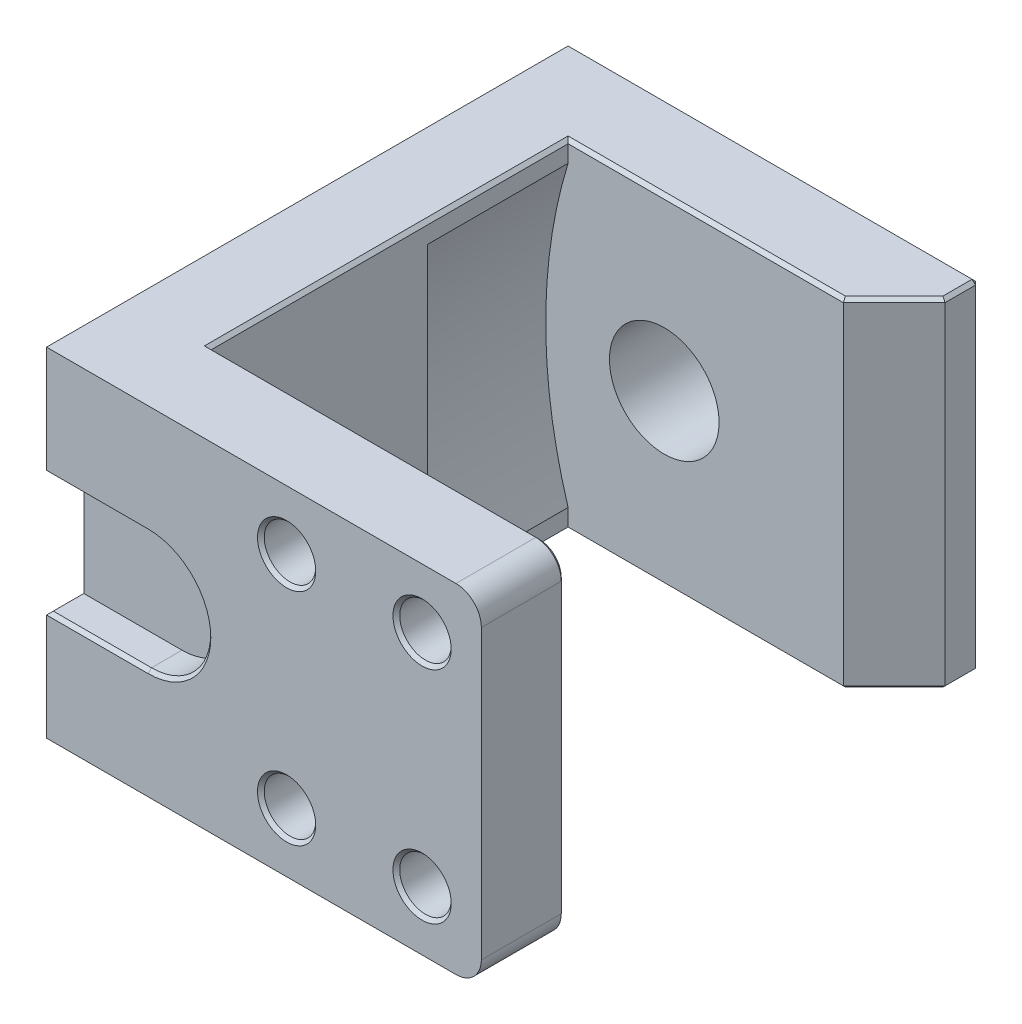
SolidWorks part; units mm, degrees
other "标注1"
sketch "草图9" plane through (-10.48, 10, -1.55) normal (-0.4516, 0.1897, -0.8718) x (-0.888, 0, 0.4599)
material "7075-T6 (SN)"
ref_plane "前视基准面" through (0, 0, 0) normal (0, 0, 1) x (1, 0, 0)
ref_plane "上视基准面" through (0, 0, 0) normal (0, 1, 0) x (1, 0, 0)
ref_plane "右视基准面" through (0, 0, 0) normal (1, 0, 0) x (0, 0, -1)
sketch "草图1" plane through (0, 0, 0) normal (0, 0, 1) x (1, 0, 0)
  line L1 (13.5775, 0) -> (13.5775, 10)
  line L2 (13.5775, 0) -> (13.5775, -10)
  line L4 (-10.48, 0) -> (-10.48, 10)
  line L5 (-10.48, 10) -> (13.5775, 10)
  line L6 (13.5775, -10) -> (-10.48, -10)
  line L7 (-10.48, -10) -> (-10.48, 0)
  circle A0 centre (0, 0) radius 3.2375
extrude "凸台-拉伸1" add sketch "草图1" along normal blind 5
sketch "草图2" plane through (0, 0, 0) normal (0, 0, 1) x (1, 0, 0)
  circle A0 centre (0, 5.6) radius 1.265
  circle A1 centre (0, -5.6) radius 1.265
extrude "切除-拉伸1" cut sketch "草图2" along normal blind 2.85
chamfer "倒角1" distance 0.2 angle 45 2 edges at (1.265, -5.6, 0) (1.265, 5.6, 0)
sketch "草图5" plane through (0, 0, 0) normal (0, 0, 1) x (1, 0, 0)
  line L0 (-8.83, 7.275) -> (-10.48, 7.275)
  line L1 (-8.83, 7.275) -> (-8.83, -7.275)
  line L4 (-10.48, 10) -> (-10.48, -10) construction
  line L5 (-10.48, 7.275) -> (-10.48, -7.275)
  line L6 (-10.48, -7.275) -> (-8.83, -7.275)
extrude "凸台-拉伸2" add sketch "草图5" against normal blind 1.55 from surface starting at face at (-1.465, -5.6, 0)
chamfer "倒角2" distance 0.2 angle 45 4 edges at (-9.655, -7.275, -1.55) (-10.48, 0, -1.55) (-9.655, 7.275, -1.55) (-8.83, 0, -1.55)
fillet "圆角1" radius 0.15 4 edges at (-10.48, -7.275, -0.675) (-10.48, 7.275, -0.675) (-8.83, -7.275, -0.675) (-8.83, 7.275, -0.675)
sketch "草图6" plane through (0, 0, 0) normal (0, 0, 1) x (1, 0, 0)
  line L1 (13.5775, 10) -> (-10.48, 10) construction
  line L3 (-10.48, -10) -> (13.5775, -10) construction
  line L6 (-10.48, 10) -> (-5.68, 10)
  line L7 (-10.48, 10) -> (-10.48, -10)
  line L8 (-10.48, -10) -> (-5.68, -10)
  line L9 (-5.68, -10) -> (-5.68, 10)
extrude "凸台-拉伸3" add sketch "草图6" along normal blind 31
sketch "草图7" plane through (0, 0, 0) normal (0, 0, 1) x (1, 0, 0)
  line L1 (13.5775, 10) -> (-5.68, 10) construction
  line L2 (-6.3225, 10) -> (-6.3225, -10)
  line L3 (-5.68, -10) -> (13.5775, -10) construction
  line L9 (-6.3225, 10) -> (19.5775, 10)
  line L10 (19.5775, 10) -> (19.5775, -10)
  line L11 (19.5775, -10) -> (-6.3225, -10)
extrude "凸台-拉伸4" add sketch "草图7" against normal blind 4.92 from surface starting at face at (-8.08, 0, 31)
sketch "草图8" plane through (0, 0, 0) normal (0, 0, 1) x (1, 0, 0)
  circle A4 centre (3.6975, 6.5) radius 1.52
  circle A5 centre (11.6975, 6.5) radius 1.52
  circle A6 centre (11.6975, -6.5) radius 1.52
  circle A7 centre (3.6975, -6.5) radius 1.52
extrude "切除-拉伸2" cut sketch "草图8" against normal up to surface (-26.08 mm away) from surface up to face at (6.9488, 0, 26.08) starting at face at (4.5488, 0, 31)
chamfer "倒角3" distance 0.2 angle 45 4 edges at (5.2175, -6.5, 31) (13.2175, -6.5, 31) (13.2175, 6.5, 31) (5.2175, 6.5, 31)
sketch "草图10" plane through (0, 0, 0) normal (0, 0, 1) x (1, 0, 0)
  line L7 (19.5775, -10) -> (19.5775, 10)
  line L8 (19.5775, 10) -> (15.1975, 10)
  line L9 (19.5775, 10) -> (-10.48, 10) construction
  line L10 (15.1975, 10) -> (15.1975, -10)
  line L11 (-10.48, -10) -> (19.5775, -10) construction
  line L12 (15.1975, -10) -> (19.5775, -10)
extrude "切除-拉伸3" cut sketch "草图10" against normal up to surface from surface up to face at (-5.9204, 0, 0) starting at face at (5.4175, -6.5, 31)
fillet "圆角2" radius 1.5 2 edges at (15.1975, -10, 28.54) (15.1975, 10, 28.54)
sketch "草图11" plane through (0, 0, 0) normal (0, 0, 1) x (1, 0, 0)
  line L2 (-4.48, 3.5) -> (-10.48, 3.5)
  line L5 (-10.48, 10) -> (-10.48, -10) construction
  line L6 (-10.48, 3.5) -> (-10.48, -3.5)
  line L7 (-10.48, -3.5) -> (-4.48, -3.5)
  arc A1 (-4.48, 3.5) -> (-4.48, -3.5) centre (-4.48, 0) cw
extrude "切除-拉伸4" cut sketch "草图11" against normal blind 2 from surface starting at face at (5.4175, -6.5, 31)
sketch "草图13" plane through (0, 0, 0) normal (0, 0, 1) x (1, 0, 0)
  line L3 (12.399, 10) -> (12.399, -10)
  line L4 (12.399, 10) -> (9.199, 10)
  line L5 (13.6975, 10) -> (-10.48, 10) construction
  line L6 (9.199, 10) -> (9.199, -10)
  line L7 (9.199, -10) -> (12.399, -10)
extrude "凸台-拉伸5" add sketch "草图13" along normal up to surface (5 mm away) from surface up to face at (3.2375, 0, 5) starting at face at (-5.9204, 0, 0)
chamfer "倒角5" distance 3 angle 45 1 edges at (13.5775, 0, 5)
sketch "草图14" plane through (0, 0, 0) normal (0, 0, 1) x (1, 0, 0)
  line L1 (13.6975, 10) -> (-10.48, 10) construction
  line L2 (-10.48, -10) -> (13.6975, -10) construction
  line L3 (-5.2843, 10) -> (-5.2843, -10)
  arc A4 (-5.2843, 10) -> (-5.2843, -10) centre (23, 0) ccw
extrude "切除-拉伸5" cut sketch "草图14" along normal blind 7 from surface starting at face at (2.4487, 0, 5)
chamfer "倒角7" distance 1.3 angle 45 1 edges at (-5.68, 0, 12)
chamfer "倒角8" distance 0.2 angle 45 22 edges at (1.5488, -10, 0) (1.5487, 10, 0) (2.4487, 10, 5) (2.4488, -10, 5) (-7.48, -3.5, 31) (-0.98, 0, 31) (-7.48, 3.5, 31) (4.0088, -10, 26.08) (14.7582, -9.5607, 26.08) (15.1975, 0, 26.08) (14.7582, 9.5607, 26.08) (-5.68, -10, 15.54) (4.0088, 10, 26.08) (-5.68, 10, 15.54) (12.0775, 10, 3.5) (13.5775, 10, 1) (13.5775, 0, 0) (13.5775, -10, 1) (12.0775, -10, 3.5) (-10.48, -3.5, 30) (-10.48, 0, 29) (-10.48, 3.5, 30)
